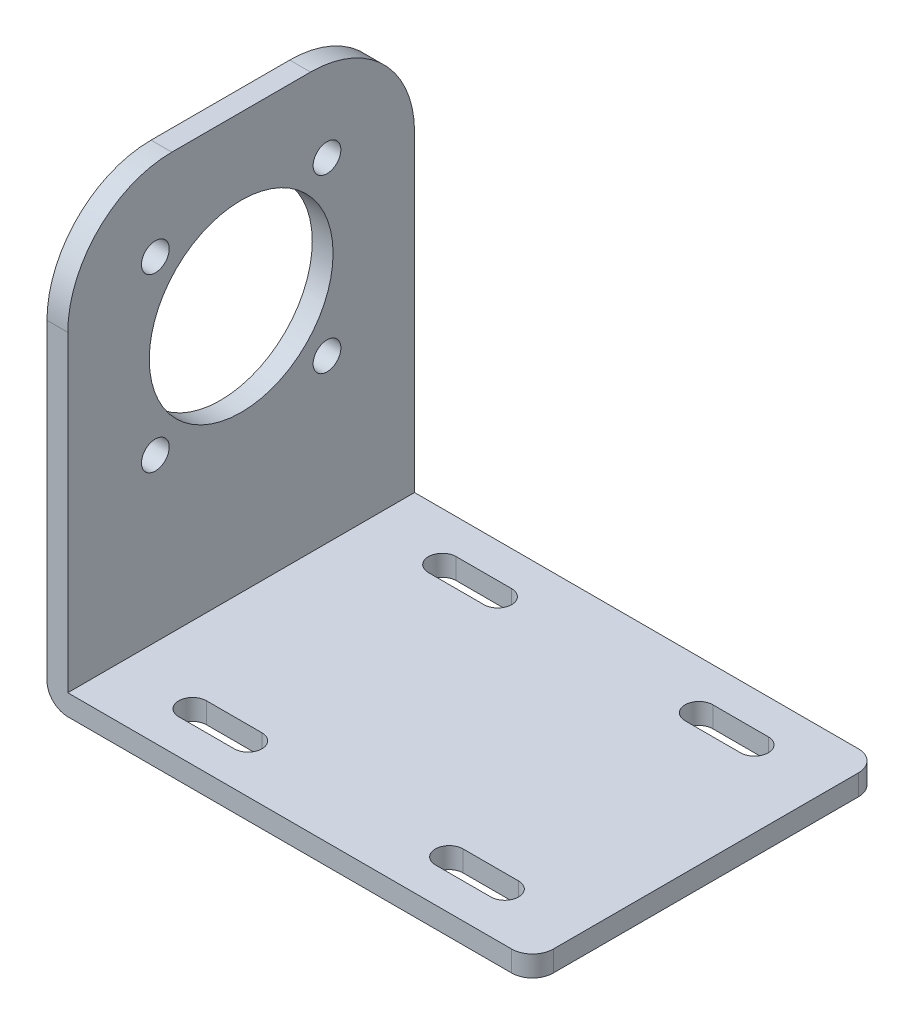
SolidWorks part; units mm, degrees
material "AISI 316 Stainless Steel Sheet (SS)"
ref_plane "Front Plane" through (0, 0, 0) normal (0, 0, 1) x (1, 0, 0)
ref_plane "Top Plane" through (0, 0, 0) normal (0, 1, 0) x (1, 0, 0)
ref_plane "Right Plane" through (0, 0, 0) normal (1, 0, 0) x (0, 0, -1)
sketch "Sketch1" plane through (0, 0, 0) normal (0, 1, 0) x (1, 0, 0)
  line L0 (12, 50) -> (12, 0) construction
  line L1 (0, 0) -> (70, 0)
  line L2 (0, 0) -> (0, 50)
  line L3 (0, 50) -> (70, 50)
  line L4 (70, 0) -> (70, 50)
  line L5 (61, 50) -> (61, 0) construction
  line L6 (0, 45) -> (70, 45) construction
  line L7 (14, 43) -> (22, 43) construction
  line L8 (14, 45) -> (22, 45)
  line L9 (14, 41) -> (22, 41)
  line L10 (51, 43) -> (59, 43) construction
  line L11 (51, 45) -> (59, 45)
  line L12 (51, 41) -> (59, 41)
  line L13 (0, 25) -> (70, 25) construction
  line L14 (51, 7) -> (59, 7) construction
  line L15 (51, 5) -> (59, 5)
  line L16 (51, 9) -> (59, 9)
  line L17 (14, 7) -> (22, 7) construction
  line L18 (14, 5) -> (22, 5)
  line L19 (14, 9) -> (22, 9)
  arc A0 (14, 45) -> (14, 41) centre (14, 43) ccw
  arc A1 (22, 41) -> (22, 45) centre (22, 43) ccw
  arc A2 (51, 45) -> (51, 41) centre (51, 43) ccw
  arc A3 (59, 41) -> (59, 45) centre (59, 43) ccw
  arc A4 (51, 5) -> (51, 9) centre (51, 7) cw
  arc A5 (59, 9) -> (59, 5) centre (59, 7) cw
  arc A6 (14, 5) -> (14, 9) centre (14, 7) cw
  arc A7 (22, 9) -> (22, 5) centre (22, 7) cw
  point P13 (18, 43)
  point P20 (55, 43)
  point P29 (55, 7)
  point P36 (18, 7)
  dimension "D7" = 8
  dimension "D1" = 50
  dimension "D2" = 70
  dimension "D3" = 12
  dimension "D4" = 9
  dimension "D5" = 5
  dimension "D6" = 4
  dimension "D8" = 4
  dimension "D9" = 8
extrude "Boss-Extrude1" add sketch "Sketch1" along normal blind 3
sketch "Sketch2" plane through (0, 3, 0) normal (0, 1, 0) x (1, 0, 0)
  line L0 (0, 0) -> (70, 0) construction
  line L1 (0, 50) -> (3, 50)
  line L2 (0, 50) -> (0, 0)
  line L3 (0, 0) -> (3, 0)
  line L4 (3, 50) -> (3, 0)
  dimension "D1" = 3
extrude "Boss-Extrude2" add sketch "Sketch2" along normal blind 60
sketch "Sketch3" plane through (0, 0, 0) normal (-1, 0, 0) x (0, 0, 1)
  line L0 (-25, 63) -> (-25, 0) construction
  line L1 (-50, 63) -> (0, 63) construction
  line L2 (-50, 0) -> (0, 0) construction
  circle A0 centre (-25, 38.75) radius 13.25
  circle A1 centre (-25, 38.75) radius 17.5 construction
  circle A2 centre (-25, 56.25) radius 2
  circle A3 centre (-12.6256, 51.1244) radius 2
  circle A4 centre (-7.5, 38.75) radius 2
  circle A5 centre (-12.6256, 26.3756) radius 2
  circle A6 centre (-25, 21.25) radius 2
  circle A7 centre (-37.3744, 26.3756) radius 2
  circle A8 centre (-42.5, 38.75) radius 2
  circle A9 centre (-37.3744, 51.1244) radius 2
  point P27 (-25, 38.75)
  dimension "D1" = 26.5
  dimension "D3" = 35
  dimension "D4" = 4
  dimension "D2" = 24.25
  dimension "D5" = 8
extrude "Cut-Extrude1" cut sketch "Sketch3" against normal blind 60 contours A0 | A5 | A3 | A9 | A7 region at (0, 38.75, -25) region at (0, 51.1244, -12.6256) region at (0, 26.3756, -12.6256) region at (0, 26.3756, -37.3744) region at (0, 51.1244, -37.3744)
fillet "Fillet1" radius 15 2 edges at (1.5, 63, -50) (1.5, 63, 0)
fillet "Fillet2" radius 3 3 edges at (0, 0, -25) (70, 1.5, 0) (70, 1.5, -50)
